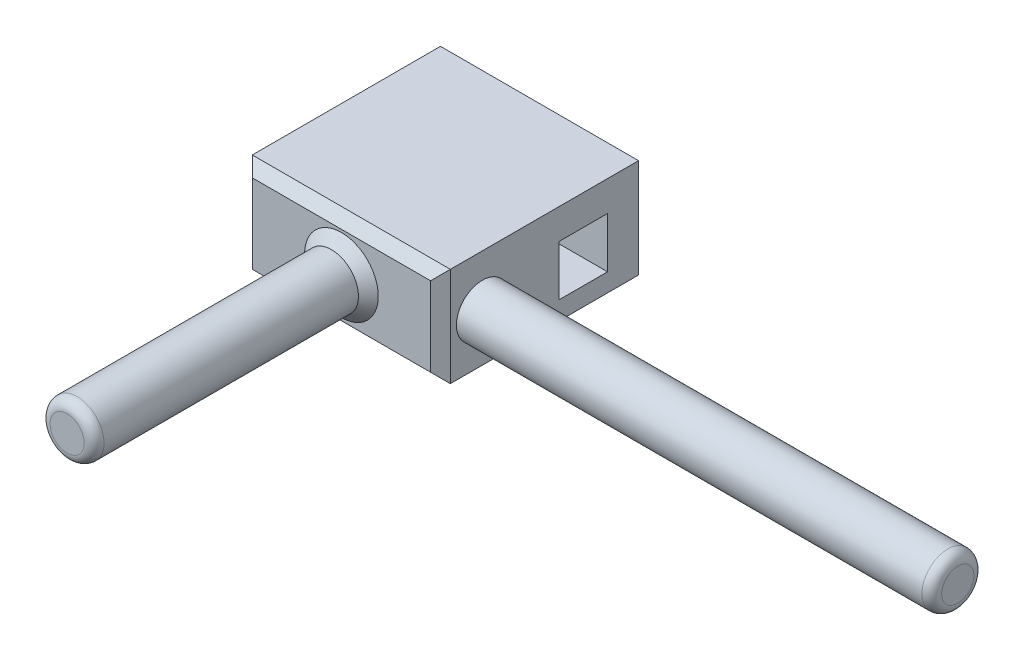
SolidWorks part; units mm, degrees
ref_plane "Front" through (0, 0, 0) normal (0, 0, 1) x (1, 0, 0)
ref_plane "Top" through (0, 0, 0) normal (0, 1, 0) x (1, 0, 0)
ref_plane "Right" through (0, 0, 0) normal (1, 0, 0) x (0, 0, -1)
sketch "Sketch1" plane through (0, 0, 0) normal (0, 0, 1) x (1, 0, 0)
  line L0 (0, 10) -> (20, 10)
  line L1 (20, 10) -> (20, 0)
  line L2 (20, 0) -> (0, 0)
  line L3 (0, 0) -> (0, 10)
  point P2 (-12.7329, 10.2174)
  point P5 (5.3416, 6.9876)
  dimension "D1" = 10
  dimension "D2" = 20
extrude "Boss-Extrude1" add sketch "Sketch1" along normal blind 10 and the other way blind 10
sketch "Sketch3" plane through (0, 0, 10) normal (0, 0, 1) x (1, 0, 0)
  line L0 (0, 10) -> (20, 0) construction
  circle A0 centre (10, 5) radius 2.7207
  point P2 (0, 0)
  point P7 (0, 0)
  point P8 (10, 5)
extrude "Boss-Extrude2" add sketch "Sketch3" along normal blind 27.6955
sketch "Sketch6" plane through (20, 0, 0) normal (1, 0, 0) x (0, 0, -1)
  line L1 (1.987, 6.9498) -> (6.8651, 6.9498)
  line L2 (1.987, 6.9498) -> (1.987, 1.8493)
  line L3 (1.987, 1.8493) -> (6.8651, 1.8493)
  line L4 (6.8651, 6.9498) -> (6.8651, 1.8493)
  circle A0 centre (-5.7644, 4.8067) radius 2.6262
  point P6 (0, 0)
extrude "Boss-Extrude3" add sketch "Sketch6" along normal blind 48 contours A0
sketch "Sketch7" plane through (20, 0, 0) normal (1, 0, 0) x (0, 0, -1)
extrude "Cut-Extrude2" cut sketch "Sketch6<5>" against normal blind 48 contours L4 L1 L2 L3 region at (20, 4.3996, -4.426)
sketch "Sketch6<5>" plane through (20, 0, 0) normal (1, 0, 0) x (0, 0, -1) same geometry as "Sketch6"
fillet "Fillet1" radius 1 1 edges at (12.7207, 5, 37.6955)
chamfer "Chamfer1" distance 1 angle 45 5 edges at (10, 10, 10) (20, 5, 10) (10, 0, 10) (0, 5, 10) (7.2793, 5, 10)
fillet "Fillet5" radius 1 1 edges at (68, 4.8067, 3.1382)
